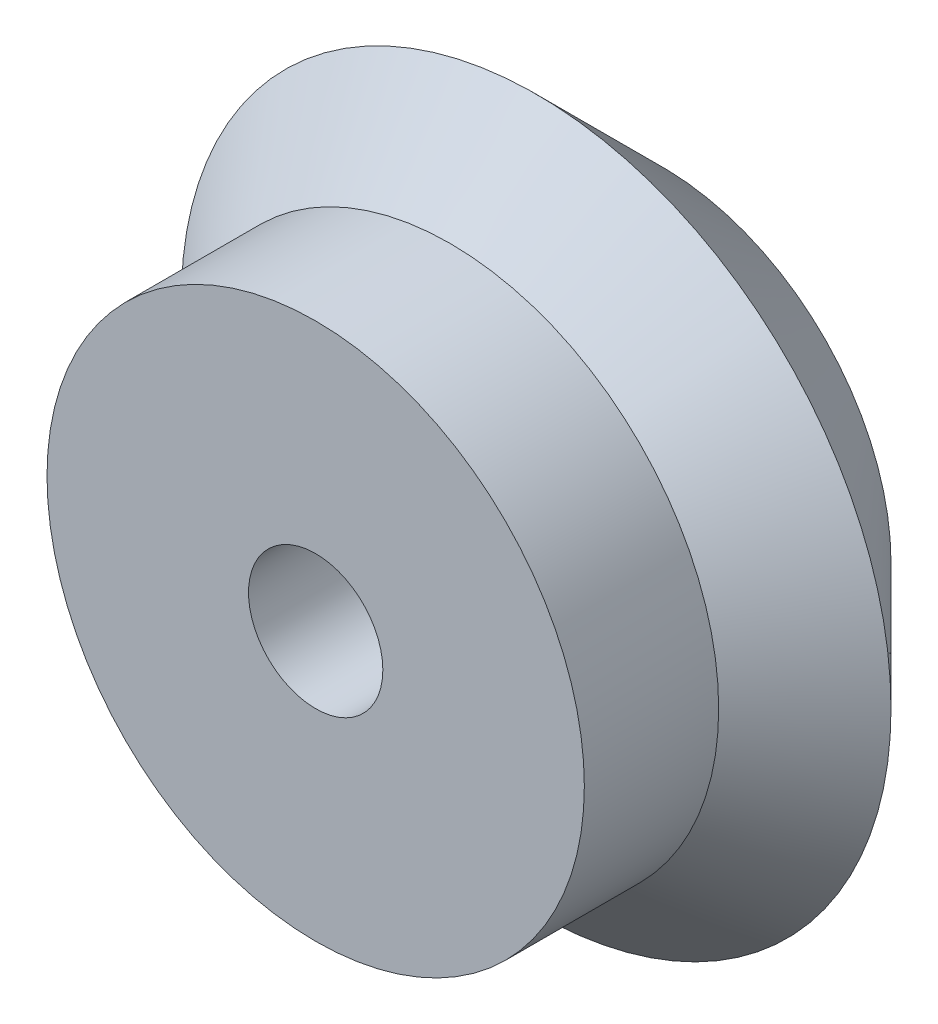
SolidWorks part; units mm, degrees
ref_plane "Front Plane" through (0, 0, 0) normal (0, 0, 1) x (1, 0, 0)
ref_plane "Top Plane" through (0, 0, 0) normal (0, 1, 0) x (1, 0, 0)
ref_plane "Right Plane" through (0, 0, 0) normal (1, 0, 0) x (0, 0, -1)
sketch "Sketch1" plane through (0, 0, 0) normal (0, 0, 1) x (1, 0, 0)
  circle A0 centre (0, 0) radius 30
  circle A1 centre (0, 0) radius 7.5
  dimension "D1" = 60
  dimension "D2" = 15
extrude "Boss-Extrude1" add sketch "Sketch1" along normal blind 15
sketch "Sketch2" plane through (0, 0, 0) normal (0, 1, 0) x (1, 0, 0)
  line L0 (30, 0) -> (39.62, 9.62)
  line L1 (30, 0) -> (57.0538, 0) construction
  line L2 (0, 0) -> (0, 25.6505) construction
  line L3 (-30, 0) -> (-39.62, 9.62)
  line L4 (39.62, 9.62) -> (25.4779, 23.7621)
  line L5 (25.4779, 23.7621) -> (17.9678, 17)
  line L6 (17.9678, 17) -> (-17.9678, 17)
  line L7 (-30, -15) -> (30, -15) construction
  line L8 (-25.4779, 23.7621) -> (-17.9678, 17)
  line L9 (-39.62, 9.62) -> (-25.4779, 23.7621)
  line L10 (30, 0) -> (-30, 0)
  line L11 (7.5, 17) -> (7.5, 0)
  point P18 (0, 17)
  dimension "D1" = 45
  dimension "D2" = 79.24
  dimension "D3" = 20
  dimension "D4" = 24.62
  dimension "D5" = 42
  dimension "D6" = 32
  dimension "D7" = 7.5
revolve "Revolve4" add sketch "Sketch2" angle 360 about L2 region at (21.8614, 0, -9.6509)
